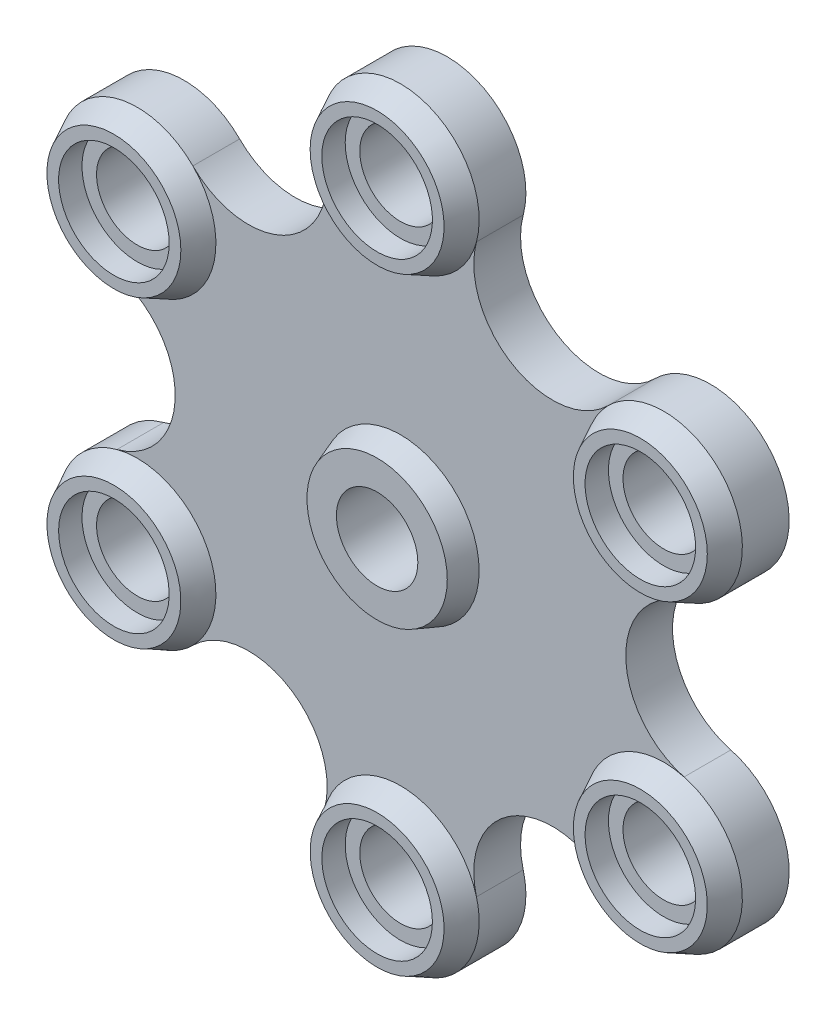
SolidWorks part; units mm, degrees
material "AISI 1035 Steel (SS)"
ref_plane "Front Plane" through (0, 0, 0) normal (0, 0, 1) x (1, 0, 0)
ref_plane "Top Plane" through (0, 0, 0) normal (0, 1, 0) x (1, 0, 0)
ref_plane "Right Plane" through (0, 0, 0) normal (1, 0, 0) x (0, 0, -1)
sketch "Sketch2" plane through (0, 0, 0) normal (0, 0, 1) x (1, 0, 0)
  arc A1 (32.5, 121.2917) -> (-32.5, 121.2917) centre (0, 130) ccw
  arc A2 (32.5, 121.2917) -> (88.7917, 88.7917) centre (65, 112.5833) ccw
  arc A3 (121.2917, 32.5) -> (88.7917, 88.7917) centre (112.5833, 65) ccw
  arc A4 (121.2917, 32.5) -> (121.2917, -32.5) centre (130, 0) ccw
  arc A5 (88.7917, -88.7917) -> (121.2917, -32.5) centre (112.5833, -65) ccw
  arc A6 (88.7917, -88.7917) -> (32.5, -121.2917) centre (65, -112.5833) ccw
  arc A7 (-32.5, -121.2917) -> (32.5, -121.2917) centre (0, -130) ccw
  arc A8 (-32.5, -121.2917) -> (-88.7917, -88.7917) centre (-65, -112.5833) ccw
  arc A9 (-121.2917, -32.5) -> (-88.7917, -88.7917) centre (-112.5833, -65) ccw
  arc A10 (-121.2917, -32.5) -> (-121.2917, 32.5) centre (-130, 0) ccw
  arc A11 (-88.7917, 88.7917) -> (-121.2917, 32.5) centre (-112.5833, 65) ccw
  arc A12 (-88.7917, 88.7917) -> (-32.5, 121.2917) centre (-65, 112.5833) ccw
  circle A18 centre (0, 130) radius 17.4167
  circle A19 centre (112.5833, 65) radius 17.4167
  circle A20 centre (112.5833, -65) radius 17.4167
  circle A21 centre (0, -130) radius 17.4167
  circle A22 centre (-112.5833, -65) radius 17.4167
  circle A23 centre (-112.5833, 65) radius 17.4167
  point P29 (0, 0)
  point P34 (0, 0)
  dimension "D2" = 12
extrude "Boss-Extrude1" add sketch "Sketch2" along normal blind 20
sketch "Sketch4" plane through (0, 0, 0) normal (1, 0, 0) x (0, 0, -1)
  line L0 (-20, 163.6465) -> (-30, 158.6465)
  line L2 (-20, 163.6465) -> (-20, 153.6465)
  line L3 (-20, 153.6465) -> (-30, 153.6465)
  line L4 (-30, 158.6465) -> (-30, 153.6465)
  dimension "D1" = 10
sketch "Sketch5" plane through (0, 0, 0) normal (1, 0, 0) x (0, 0, -1)
  line L1 (0, 121.2917) -> (0, 163.6465) construction
  line L2 (0, 130) -> (-63.2018, 130) construction
  line L3 (-63.2018, 130) -> (40.5369, 130) construction
revolve "Revolve1" add sketch "Sketch4" angle 360 about L2
sketch "Sketch7" plane through (0, 0, 0) normal (0, 0, 1) x (1, 0, 0)
  circle A0 centre (0, 0) radius 130 construction
  circle A1 centre (0, 0) radius 17.4167
  circle A2 centre (0, 130) radius 17.4167 construction
extrude "Cut-Extrude2" cut sketch "Sketch7" along normal blind 20
pattern_circular "CirPattern1" count 6 over 360 about axis through (0, 0, 20) along (0, 0, 1) of "Revolve1"
sketch "Sketch8" plane through (0, 0, 0) normal (0, 0, 1) x (1, 0, 0)
  circle A0 centre (0, 0) radius 33.6465
  arc A1 (-32.5, 121.2917) -> (32.5, 121.2917) centre (0, 130) ccw construction
extrude "Boss-Extrude2" add sketch "Sketch8" along normal offset from surface (30 mm away) 30 up to plane "Front Plane"
sketch "Sketch9" plane through (0, 0, 0) normal (0, 0, 1) x (1, 0, 0)
  circle A0 centre (0, 0) radius 17.4167
  circle A1 centre (0, 130) radius 17.4167 construction
sketch "Sketch10" plane through (0, 0, 0) normal (0, 0, 1) x (1, 0, 0)
  circle A0 centre (0, 0) radius 17.4167
extrude "Cut-Extrude3" cut sketch "Sketch10" along normal blind 30
chamfer "Chamfer1" distance 10 angle 20 1 edges at (33.6465, 0, 30) first distance on face at (33.6465, 0, 20)
sketch "Sketch13" plane through (0, 0, 0) normal (0, 0, 1) x (1, 0, 0)
  circle A0 centre (-0.0714, 2.0957) radius 70
  circle A1 centre (-113.6487, 65.3429) radius 60
  circle A2 centre (-2.0957, 132.0957) radius 60
  circle A3 centre (-42.1057, 72.3713) radius 11.8874
  circle A4 centre (-42.1057, 72.3713) radius 9
  dimension "D1" = 140
  dimension "D2" = 120
  dimension "D3" = 120
  dimension "D7" = 23.7748
  dimension "D8" = 18
  dimension "D4" = 130
  dimension "D5" = 130
  dimension "D6" = 130
